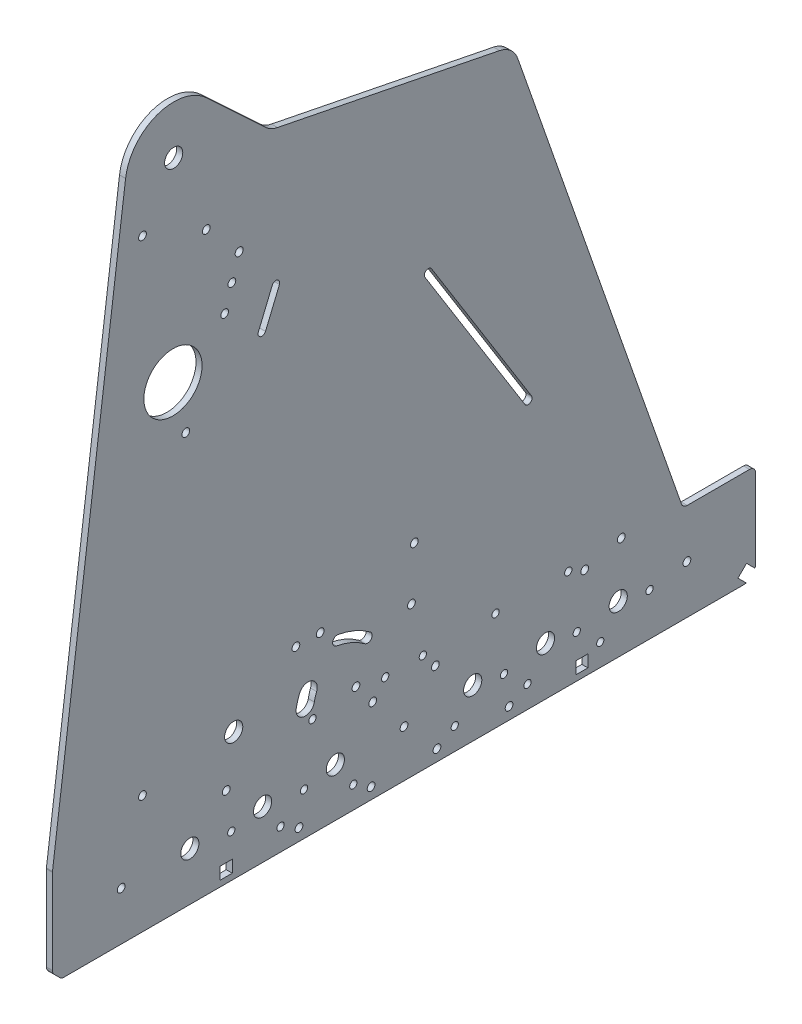
SolidWorks part; units mm, degrees
ref_plane "Front Plane" through (0, 0, 0) normal (0, 0, 1) x (1, 0, 0)
ref_plane "Top Plane" through (0, 0, 0) normal (0, 1, 0) x (1, 0, 0)
ref_plane "Right Plane" through (0, 0, 0) normal (1, 0, 0) x (0, 0, -1)
sketch "Sketch1" plane through (0, 0, 0) normal (1, 0, 0) x (0, 0, -1)
  line L0 (-184.15, -24.6062) -> (184.15, -24.6062)
  line L1 (184.15, -24.6062) -> (184.15, 26.1938)
  line L2 (184.15, 26.1938) -> (146.05, 26.1937)
  line L3 (146.05, 26.1937) -> (57.15, 280.1938)
  line L5 (-145.839, 321.5609) -> (-184.15, 26.1938)
  line L6 (-184.15, 26.1938) -> (-184.15, -24.6062)
  line L7 (-184.15, 350.0437) -> (184.15, 350.0437) construction
  line L8 (57.15, 280.1938) -> (-69.85, 305.5938)
  line L9 (-69.85, 305.5938) -> (-103.3099, 336.854)
  arc A0 (-103.3099, 336.854) -> (-145.839, 321.5609) centre (-120.65, 318.2937) ccw
  point P8 (0, -24.6062)
  dimension "D1" = 368.3
  dimension "D7" = 25.4
  dimension "D2" = 50.8
  dimension "D3" = 38.1
  dimension "D4" = 24.6062
  dimension "D5" = 374.65
  dimension "D6" = 304.8
  dimension "D8" = 342.9
  dimension "D9" = 127
  dimension "D10" = 304.8
  dimension "D11" = 25.4
  dimension "D12" = 127
extrude "Boss-Extrude1" add sketch "Sketch1" along normal blind 3.175
chamfer "Chamfer1" distance 4.7625 angle 45 2 edges at (1.5875, -24.6062, 184.15) (1.5875, -24.6062, -184.15)
fillet "Fillet1" radius 12.7 2 edges at (1.5875, 305.5938, 69.85) (1.5875, 280.1938, -57.15)
fillet "Fillet2" radius 3.175 3 edges at (1.5875, 26.1938, 184.15) (1.5875, 26.1938, -184.15) (1.5875, 26.1937, -146.05)
fillet "Fillet3" radius 3.175 4 edges at (1.5875, -19.8438, -184.15) (1.5875, -24.6062, -179.3875) (1.5875, -19.8437, 184.15) (1.5875, -24.6062, 179.3875)
sketch "Sketch16" plane through (3.175, 0, 0) normal (1, 0, 0) x (0, 0, -1)
  circle A0 centre (112.1746, 0.7937) radius 4.7625
  circle A1 centre (74.0746, 0.7937) radius 4.7625
  circle A2 centre (35.9746, 0.7937) radius 4.7625
  circle A3 centre (-35.9746, 0.7938) radius 4.7625
  circle A4 centre (-74.0746, 0.7938) radius 4.7625
  circle A5 centre (-112.1746, 0.7937) radius 4.7625
  dimension "D1" = 9.525
  dimension "D2" = 9.525
extrude "Cut-Extrude1" cut sketch "Sketch16" against normal up to next
sketch "Sketch25" plane through (3.175, 0, 0) normal (1, 0, 0) x (0, 0, -1)
  circle A0 centre (102.7672, -13.0003) radius 1.905 construction
  circle A1 centre (86.0486, 27.3622) radius 1.905 construction
  circle A2 centre (128.5804, -2.3081) radius 1.905 construction
  circle A3 centre (102.7672, -13.0003) radius 1.905
  circle A4 centre (86.0486, 27.3622) radius 1.905
  circle A5 centre (128.5804, -2.3081) radius 1.905
  circle A6 centre (64.6672, -13.0003) radius 1.905 construction
  circle A8 centre (-9.8486, 27.3622) radius 1.905 construction
  circle A10 centre (-47.9486, 27.3622) radius 1.905 construction
  circle A11 centre (-90.4804, -2.3081) radius 1.905 construction
  circle A12 centre (-64.6672, -13.0003) radius 1.905 construction
  circle A14 centre (-52.3804, -2.3081) radius 1.905 construction
  circle A15 centre (-26.5672, -13.0003) radius 1.905 construction
  circle A16 centre (9.8486, 27.3622) radius 1.905 construction
  circle A17 centre (26.5672, -13.0003) radius 1.905 construction
  circle A18 centre (47.9486, 27.3622) radius 1.905 construction
  circle A19 centre (52.3804, -2.3081) radius 1.905 construction
  circle A20 centre (90.4804, -2.3081) radius 1.905 construction
  circle A21 centre (-9.8486, 27.3622) radius 1.905
  circle A23 centre (-47.9486, 27.3622) radius 1.905
  circle A24 centre (-90.4804, -2.3081) radius 1.905
  circle A25 centre (-64.6672, -13.0003) radius 1.905
  circle A27 centre (-52.3804, -2.3081) radius 1.905
  circle A28 centre (-26.5672, -13.0003) radius 1.905
  circle A29 centre (9.8486, 27.3622) radius 1.905
  circle A30 centre (26.5672, -13.0003) radius 1.905
  circle A31 centre (47.9486, 27.3622) radius 1.905
  circle A32 centre (64.6672, -13.0003) radius 1.905
  circle A33 centre (52.3804, -2.3081) radius 1.905
  circle A34 centre (90.4804, -2.3081) radius 1.905
extrude "Cut-Extrude4" cut sketch "Sketch25" against normal up to next
sketch "Sketch23" plane through (3.175, 0, 0) normal (1, 0, 0) x (0, 0, -1)
  point P0 (-55.0246, -18.3223)
  point P6 (-93.1246, 17.5943)
  point P9 (-17.2515, -18.6426)
  point P12 (-16.4124, 19.3854)
  point P15 (16.4124, 19.3854)
  point P18 (17.2515, -18.6426)
  point P21 (55.0246, -18.3223)
  point P35 (3.8736, 53.6853)
  point P38 (113.7728, 28.6594)
  point P41 (-137.0088, 37.226)
hole_wizard "#8 (0.16) Diameter Hole1" positions "Sketch23" profile "Sketch24" hole size "#8" standard "ANSI Inch" end condition up to next
sketch "Sketch24" plane through (3.175, -18.3223, 55.0246) normal (0, 1, 0) x (0, 0, -1)
  line L0 (0, 0) -> (0, 3.175)
  line L1 (0, 3.175) -> (2.032, 3.175)
  line L2 (2.032, 3.175) -> (2.032, 0)
  line L5 (2.032, 0) -> (0, 0)
  line L11 (0, -6.35) -> (0, 107.95) construction
  dimension "Thru Hole Dia." = 4.064
  dimension "Thru Hole Depth" = 3.175
sketch "Sketch22" plane through (3.175, 0, 0) normal (1, 0, 0) x (0, 0, -1)
  line L0 (-96.2996, -15.1473) -> (-89.9496, -15.1473) construction
  line L1 (-96.2996, -15.1473) -> (-89.9496, -15.1473)
  line L2 (-96.2996, -15.1473) -> (-96.2996, -21.4973)
  line L3 (-96.2996, -21.4973) -> (-89.9496, -21.4973)
  line L4 (-89.9496, -15.1473) -> (-89.9496, -21.4973)
  line L5 (-96.2996, -15.1473) -> (-89.9496, -21.4973) construction
  line L6 (-96.2996, -21.4973) -> (-89.9496, -15.1473) construction
  line L7 (-89.9496, -15.1473) -> (-89.9496, -19.8734) construction
  line L77 (179.3875, -24.6062) -> (183.8776, -20.1161)
  line L78 (179.3875, -24.6062) -> (174.8974, -20.1161)
  line L79 (183.8776, -20.1161) -> (179.3875, -15.626)
  line L80 (174.8974, -20.1161) -> (179.3875, -15.626)
  line L81 (180.3174, -23.6763) -> (183.2201, -20.7737) construction
  line L82 (-178.0724, -24.6062) -> (178.0724, -24.6062) construction
  line L84 (89.9496, -21.4973) -> (96.2996, -21.4973)
  line L85 (89.9496, -21.4973) -> (89.9496, -15.1473)
  line L86 (89.9496, -15.1473) -> (96.2996, -15.1473)
  line L87 (96.2996, -21.4973) -> (96.2996, -15.1473)
  line L88 (89.9496, -21.4973) -> (96.2996, -15.1473) construction
  line L89 (89.9496, -15.1473) -> (96.2996, -21.4973) construction
  point P0 (-93.1246, -18.3223)
  point P19 (93.1246, -18.3223)
  dimension "D1" = 6.35
  dimension "D2" = 6.35
extrude "Cut-Extrude3" cut sketch "Sketch22" against normal up to next
sketch "Sketch21" plane through (3.175, 0, 0) normal (1, 0, 0) x (0, 0, -1)
  circle A0 centre (-148.1579, 0.7937) radius 2.032
  circle A2 centre (0, 0) radius 2.032
  circle A3 centre (148.1579, 0.7938) radius 2.032
  dimension "D1" = 4.064
extrude "Cut-Extrude2" cut sketch "Sketch21" against normal up to next
sketch "Sketch26" plane through (3.175, 0, 0) normal (1, 0, 0) x (0, 0, -1)
  line L0 (-145.839, 321.5609) -> (-184.1236, 26.3971) construction
  line L1 (-178.0724, -24.6062) -> (178.0724, -24.6062) construction
  circle A0 centre (-121.0218, 216.6937) radius 15.24
  dimension "D1" = 30.48
  dimension "D2" = 38.1
  dimension "D3" = 241.3
extrude "Cut-Extrude5" cut sketch "Sketch26" against normal through all
sketch "Sketch27" plane through (3.175, 0, 0) normal (1, 0, 0) x (0, 0, -1)
  circle A0 centre (-120.65, 318.2937) radius 4.7625
  dimension "D1" = 9.525
extrude "Cut-Extrude6" cut sketch "Sketch27" against normal through all
sketch "Sketch28" plane through (3.175, 0, 0) normal (1, 0, 0) x (0, 0, -1)
  line L0 (-120.65, 318.2937) -> (-103.5612, 277.2599) construction
  line L1 (-103.5612, 277.2599) -> (-86.3654, 258.566) construction
  line L2 (-86.3654, 258.566) -> (-90.1612, 246.4465) construction
  line L3 (-90.1612, 246.4465) -> (-93.9569, 234.327) construction
  line L4 (-145.839, 321.5609) -> (-184.1236, 26.3971) construction
  circle A0 centre (-93.9569, 234.327) radius 2.032
  circle A1 centre (-90.1612, 246.4465) radius 2.032
  circle A2 centre (-86.3654, 258.566) radius 2.0955
  circle A3 centre (-103.5612, 277.2599) radius 2.032
  dimension "D4" = 4.064
  dimension "D5" = 4.191
  dimension "D6" = 4.064
  dimension "D1" = 25.4
  dimension "D2" = 44.45
  dimension "D3" = 12.7
  dimension "D7" = 30
  dimension "D8" = 120
  dimension "D9" = 160
extrude "Cut-Extrude7" cut sketch "Sketch28" against normal through all
sketch "Sketch29" plane through (3.175, 0, 0) normal (1, 0, 0) x (0, 0, -1)
  line L0 (-145.839, 321.5609) -> (-184.1236, 26.3971) construction
  line L1 (-67.1375, 233.9197) -> (-74.4276, 216.3198) construction
  line L2 (-65.2602, 233.1421) -> (-72.5503, 215.5422)
  line L3 (-69.0148, 234.6973) -> (-76.305, 217.0974)
  line L4 (-67.1375, 233.9197) -> (-67.1375, 253.7354) construction
  circle A0 centre (-136.9875, 291.0697) radius 2.032
  circle A2 centre (-120.65, 318.2937) radius 4.7625 construction
  arc A4 (-65.2602, 233.1421) -> (-69.0148, 234.6973) centre (-67.1375, 233.9197) ccw
  arc A5 (-76.305, 217.0974) -> (-72.5503, 215.5422) centre (-74.4276, 216.3198) ccw
  point P8 (-70.7826, 225.1198)
  dimension "D1" = 31.75
  dimension "D2" = 4.064
  dimension "D3" = 69.85
  dimension "D4" = 12.7
  dimension "D5" = 57.15
  dimension "D6" = 19.05
  dimension "D7" = 22.5
extrude "Cut-Extrude8" cut sketch "Sketch29" against normal through all
sketch "Sketch30" plane through (3.175, 0, 0) normal (1, 0, 0) x (0, 0, -1)
  circle A8 centre (-89.211, 42.2593) radius 4.7625
  circle A9 centre (-25.1593, 30.6938) radius 2.032
  arc A10 (-51.7173, 35.4892) -> (-50.2741, 40.5715) centre (-25.1593, 30.6938) cw construction
  arc A11 (-54.7652, 42.3379) -> (-56.4665, 36.3468) centre (-25.1593, 30.6938) ccw
  arc A12 (-45.783, 38.8051) -> (-46.9681, 34.6317) centre (-25.1593, 30.6938) ccw
  arc A13 (-45.783, 38.8051) -> (-54.7652, 42.3379) centre (-50.2741, 40.5715) ccw
  arc A14 (-56.4665, 36.3468) -> (-46.9681, 34.6317) centre (-51.7173, 35.4892) ccw
  arc A15 (-34.9881, 56.6661) -> (-19.1131, 49.8125) centre (-41.7582, 19.1724) cw construction
  arc A16 (-17.6789, 51.753) -> (-34.5594, 59.0407) centre (-41.7582, 19.1724) ccw
  arc A17 (-20.5473, 47.8719) -> (-35.4169, 54.2915) centre (-41.7582, 19.1724) ccw
  arc A18 (-20.5473, 47.8719) -> (-17.6789, 51.753) centre (-19.1131, 49.8125) ccw
  arc A19 (-34.5594, 59.0407) -> (-35.4169, 54.2915) centre (-34.9881, 56.6661) ccw
  arc A20 (-19.1131, 49.8125) -> (-34.9881, 56.6661) centre (-41.7582, 19.1724) ccw construction
  circle A21 centre (94.6345, 23.8125) radius 2.032
  circle A22 centre (-56.6241, 64.5541) radius 2.032
  circle A23 centre (-43.9241, 64.5541) radius 2.032
  circle A24 centre (-56.6241, 64.5541) radius 1.905 construction
  circle A25 centre (-43.9241, 64.5541) radius 1.905 construction
  point P7 (-51.1204, 38.0658)
  point P19 (-26.6567, 54.1518)
  dimension "D2" = 9.652
  dimension "D4" = 4.064
  dimension "D1" = 4.064
  dimension ".375" = 9.525
  dimension "D3" = 4.826
extrude "Cut-Extrude9" cut sketch "Sketch30" against normal through all
sketch "Sketch31" plane through (0, 0, 0) normal (-1, 0, 0) x (0, 0, 1)
  circle A1 centre (114.3, 190.5) radius 2.032
  dimension "D1" = 114.3
  dimension "D6" = 4.064
  dimension "D2" = 190.5
extrude "Cut-Extrude10" cut sketch "Sketch31" against normal through all
sketch "Sketch34" plane through (0, 0, 0) normal (-1, 0, 0) x (0, 0, 1)
  line L0 (-65.024, 115.57) -> (-12.7, 199.39) construction
  line L1 (-66.7477, 116.646) -> (-14.4237, 200.466)
  line L2 (-63.3003, 114.494) -> (-10.9763, 198.314)
  arc A0 (-66.7477, 116.646) -> (-63.3003, 114.494) centre (-65.024, 115.57) ccw
  arc A1 (-10.9763, 198.314) -> (-14.4237, 200.466) centre (-12.7, 199.39) ccw
  point P3 (-38.862, 157.48)
  dimension "D5" = 2.032
  dimension "D1" = 115.57
  dimension "D2" = 65.024
  dimension "D3" = 199.39
  dimension "D4" = 12.7
extrude "Cut-Extrude12" cut sketch "Sketch34" against normal through all
sketch "Sketch37" plane through (3.175, 0, 0) normal (1, 0, 0) x (0, 0, -1)
  circle A0 centre (5.3975, 80.645) radius 2.032
  circle A8 centre (0, 0) radius 2.032 construction
  point P5 (5.5025, -23.168)
  dimension "D1" = 4.064
  dimension "D2" = 5.3975
  dimension "D3" = 80.645
extrude "Cut-Extrude13" cut sketch "Sketch37" against normal through all
